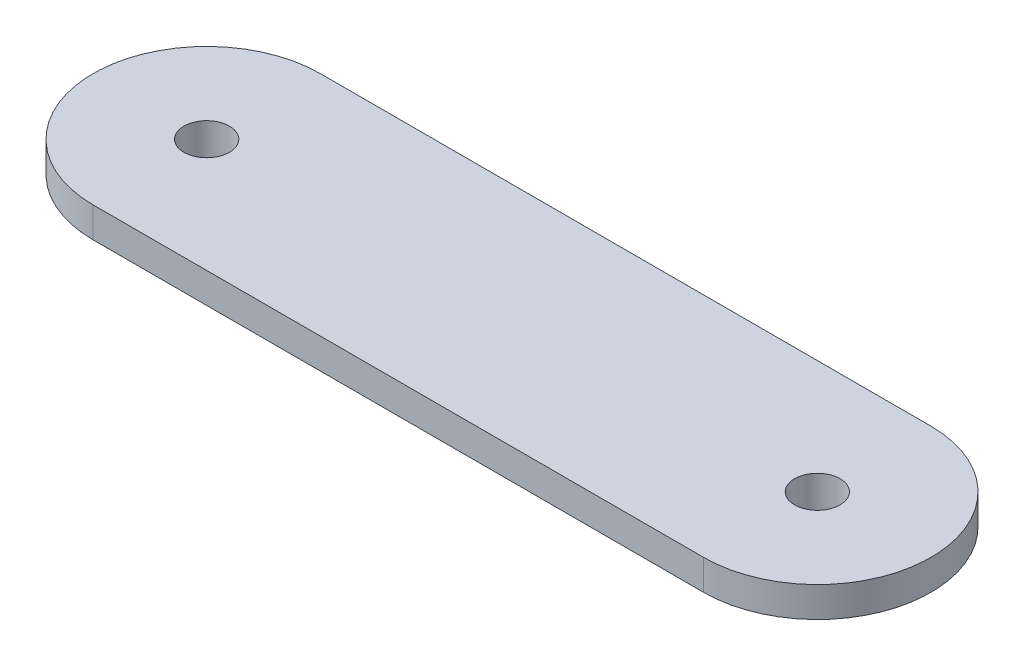
SolidWorks part; units mm, degrees
ref_plane "Front Plane" through (0, 0, 0) normal (0, 0, 1) x (1, 0, 0)
ref_plane "Top Plane" through (0, 0, 0) normal (0, 1, 0) x (1, 0, 0)
ref_plane "Right Plane" through (0, 0, 0) normal (1, 0, 0) x (0, 0, -1)
sketch "Sketch1" plane through (0, 0, 0) normal (0, 1, 0) x (1, 0, 0)
  line L0 (-20.15, 0) -> (20.15, 0) construction
  line L1 (-20.15, 7.5) -> (20.15, 7.5)
  line L2 (-20.15, -7.5) -> (20.15, -7.5)
  arc A0 (-20.15, 7.5) -> (-20.15, -7.5) centre (-20.15, 0) ccw
  arc A1 (20.15, -7.5) -> (20.15, 7.5) centre (20.15, 0) ccw
  point P3 (0, 0)
  dimension "D1" = 40.3
  dimension "D2" = 15
extrude "Boss-Extrude1" add sketch "Sketch1" along normal blind 2
sketch "Sketch2" plane through (0, 0, 0) normal (0, -1, 0) x (1, 0, 0)
  circle A0 centre (-20.15, 0) radius 1.5
  circle A1 centre (20.15, 0) radius 1.5
  dimension "D1" = 3
  dimension "D2" = 3
extrude "Cut-Extrude1" cut sketch "Sketch2" against normal through all
sketch "Sketch3" plane through (0, 0, 0) normal (0, -1, 0) x (1, 0, 0)
  line L0 (0, -4.9611) -> (0, 5.0175) construction
  circle A0 centre (20.15, 0) radius 1.5 construction
  circle A1 centre (-20.15, 0) radius 1.5 construction
  circle A2 centre (20.15, 0) radius 1.5
  circle A3 centre (-20.15, 0) radius 1.5
  circle A4 centre (-20.15, 0) radius 2
  circle A5 centre (20.15, 0) radius 2
  dimension "D1" = 4
extrude "Boss-Extrude2" add sketch "Sketch3" along normal blind 0.5
fillet "Fillet1" radius 5 2 edges at (20.15, 0, 2) (-20.15, 0, 2)
ref_axis "Axis1" through (-20.15, 2, 0) along (0, -1, 0)
ref_axis "Axis2" through (20.15, 2, 0) along (0, -1, 0)
